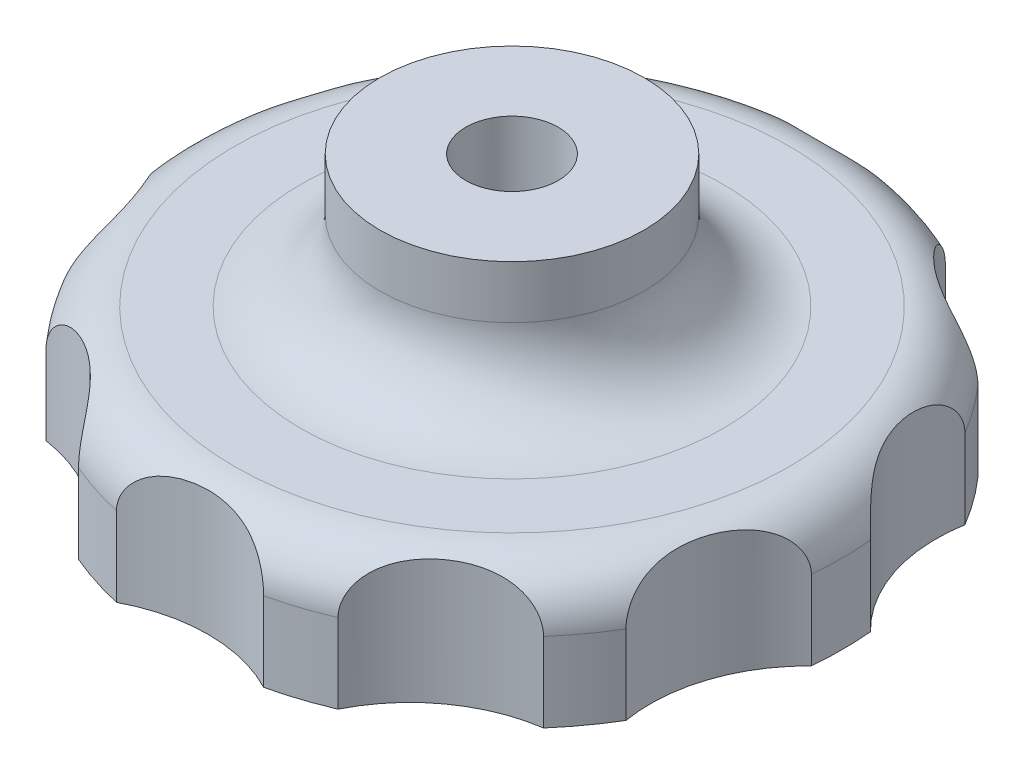
SolidWorks part; units mm, degrees
ref_plane "Plano frontal" through (0, 0, 0) normal (0, 0, 1) x (1, 0, 0)
ref_plane "Plano superior" through (0, 0, 0) normal (0, 1, 0) x (1, 0, 0)
ref_plane "Plano direito" through (0, 0, 0) normal (1, 0, 0) x (0, 0, -1)
sketch "Esboço1" plane through (0, 0, 0) normal (0, 0, 1) x (1, 0, 0)
  line L0 (0, 0) -> (12.5, 0)
  line L1 (0, 0) -> (0, 25.0998) construction
  line L2 (12.5, 0) -> (12.5, 5)
  line L3 (12.5, 5) -> (5, 5)
  line L4 (5, 5) -> (5, 10)
  line L5 (5, 10) -> (0, 10)
  line L6 (0, 10) -> (0, 0)
  dimension "D1" = 25
  dimension "D2" = 5
  dimension "D3" = 10
  dimension "D4" = 10
revolve "Revolução1" add sketch "Esboço1" angle 360 about L1
fillet "Filete1" radius 3 1 edges at (0, 5, -5)
fillet "Filete2" radius 2 1 edges at (0, 5, -12.5)
sketch "Esboço2" plane through (0, 0, 0) normal (0, -1, 0) x (1, 0, 0)
  line L0 (0, 0) -> (0, 12.5) construction
  line L1 (0, 12.5) -> (0, 17.5) construction
  circle A0 centre (0, 0) radius 12.5 construction
  circle A1 centre (0, 17.5) radius 6
  dimension "D2" = 12
  dimension "D1" = 5
extrude "Corte-extrusão1" cut sketch "Esboço2" against normal up to surface (5 mm away) up to face at (0, 5, 10.5)
ref_axis "Eixo1" through (0, 14.1552, 0) along (0, -1, 0)
pattern_circular "PadrãoCircular1" count 10 over 360 about axis through (0, 14.1552, 0) along (0, -1, 0) of "Corte-extrusão1"
sketch "Esboço3" plane through (0, 0, 0) normal (0, -1, 0) x (1, 0, 0)
  circle A0 centre (0, 0) radius 1.75
  dimension "D1" = 3.5
extrude "Corte-extrusão2" cut sketch "Esboço3" against normal up to surface (10 mm away) up to face at (0, 10, -5)
sketch "Esboço4" plane through (0, 0, 0) normal (0, -1, 0) x (1, 0, 0)
  line L1 (3.1754, 0) -> (1.5877, 2.75)
  line L2 (1.5877, 2.75) -> (-1.5877, 2.75)
  line L3 (-1.5877, 2.75) -> (-3.1754, 0)
  line L4 (-3.1754, 0) -> (-1.5877, -2.75)
  line L5 (-1.5877, -2.75) -> (1.5877, -2.75)
  line L6 (1.5877, -2.75) -> (3.1754, 0)
  circle A0 centre (0, 0) radius 2.75 construction
  dimension "D1" = 5.5
extrude "Corte-extrusão3" cut sketch "Esboço4" against normal blind 2.4
